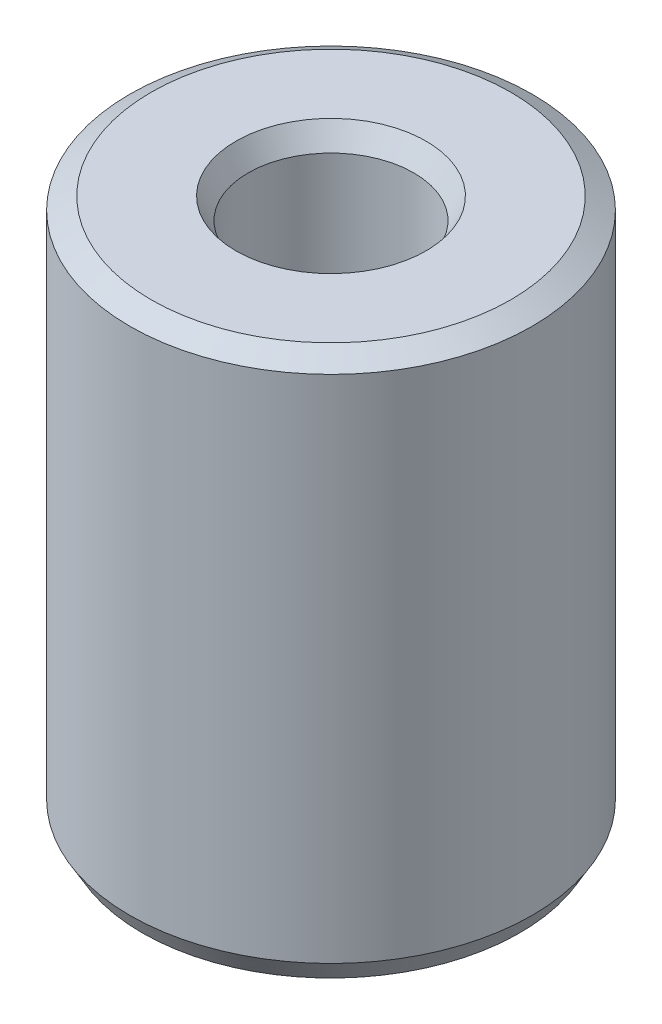
SolidWorks part; units mm, degrees
ref_plane "Front Plane" through (0, 0, 0) normal (0, 0, 1) x (1, 0, 0)
ref_plane "Top Plane" through (0, 0, 0) normal (0, 1, 0) x (1, 0, 0)
ref_plane "Right Plane" through (0, 0, 0) normal (1, 0, 0) x (0, 0, -1)
sketch "Sketch1" plane through (0, 0, 0) normal (0, 1, 0) x (1, 0, 0)
  circle A0 centre (0, 0) radius 55
  dimension "SLEEVE_OD" = 110
extrude "Boss-Extrude1" add sketch "Sketch1" along normal blind 148.7146
sketch "Sketch2" plane through (0, 0, 0) normal (0, 1, 0) x (1, 0, 0)
  circle A0 centre (0, 0) radius 22.6374
  dimension "BORE_D" = 45.2747
extrude "Cut-Extrude1" cut sketch "Sketch2" along normal through all
chamfer "Chamfer1" distance 3.3658 angle 60 4 edges at (0, 148.7146, 22.6374) (0, 0, 22.6374) (0, 0, 55) (0, 148.7146, 55) first distance on face at (0, 148.7146, 22.6374) first distance on face at (0, 0, 22.6374) first distance on face at (0, 148.7146, 55)
